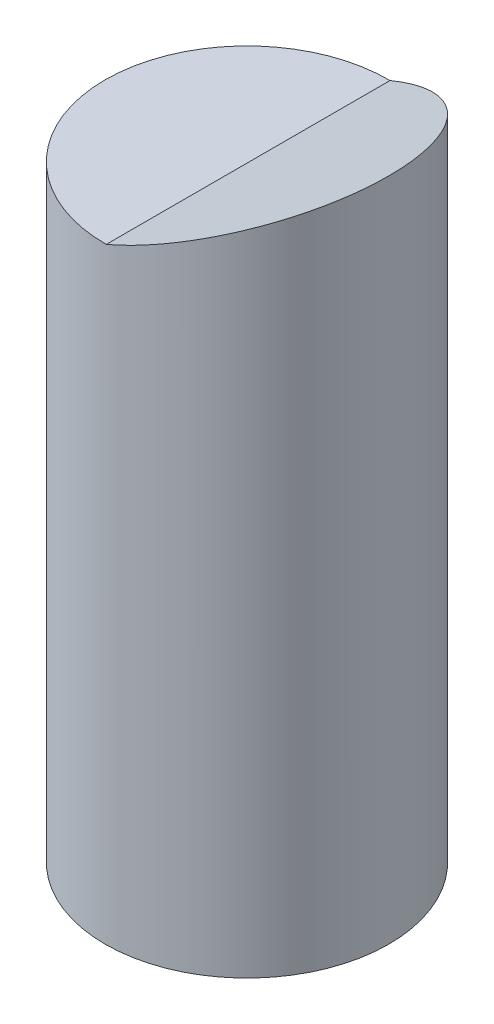
SolidWorks part; units mm, degrees
material "1060 Alloy"
ref_plane "Front Plane" through (0, 0, 0) normal (0, 0, 1) x (1, 0, 0)
ref_plane "Top Plane" through (0, 0, 0) normal (0, 1, 0) x (1, 0, 0)
ref_plane "Right Plane" through (0, 0, 0) normal (1, 0, 0) x (0, 0, -1)
sketch "Sketch1" plane through (0, 0, 0) normal (0, 1, 0) x (1, 0, 0)
  circle A0 centre (0, 0) radius 7.25
  dimension "D1" = 14.5
extrude "Boss-Extrude1" add sketch "Sketch1" along normal blind 31
sketch "Sketch2" plane through (0, 0, 0) normal (0, 0, 1) x (1, 0, 0)
  line L0 (0, 30.9746) -> (7.25, 31)
  line L1 (7.25, 31) -> (7.25, 34)
  line L2 (7.25, 34) -> (0, 30.9746)
  line L3 (0, 30.9746) -> (0, 36.6055) construction
extrude "Boss-Extrude2" add sketch "Sketch2" along normal blind 7.25 and the other way blind 7.25
sketch "Sketch3" plane through (0, 31, 0) normal (0, 1, 0) x (1, 0, 0)
  circle A0 centre (0, 0) radius 7.25
  circle A1 centre (0, 0) radius 10.6636
extrude "Cut-Extrude1" cut sketch "Sketch3" along normal blind 7.25 and the other way blind 7.25
